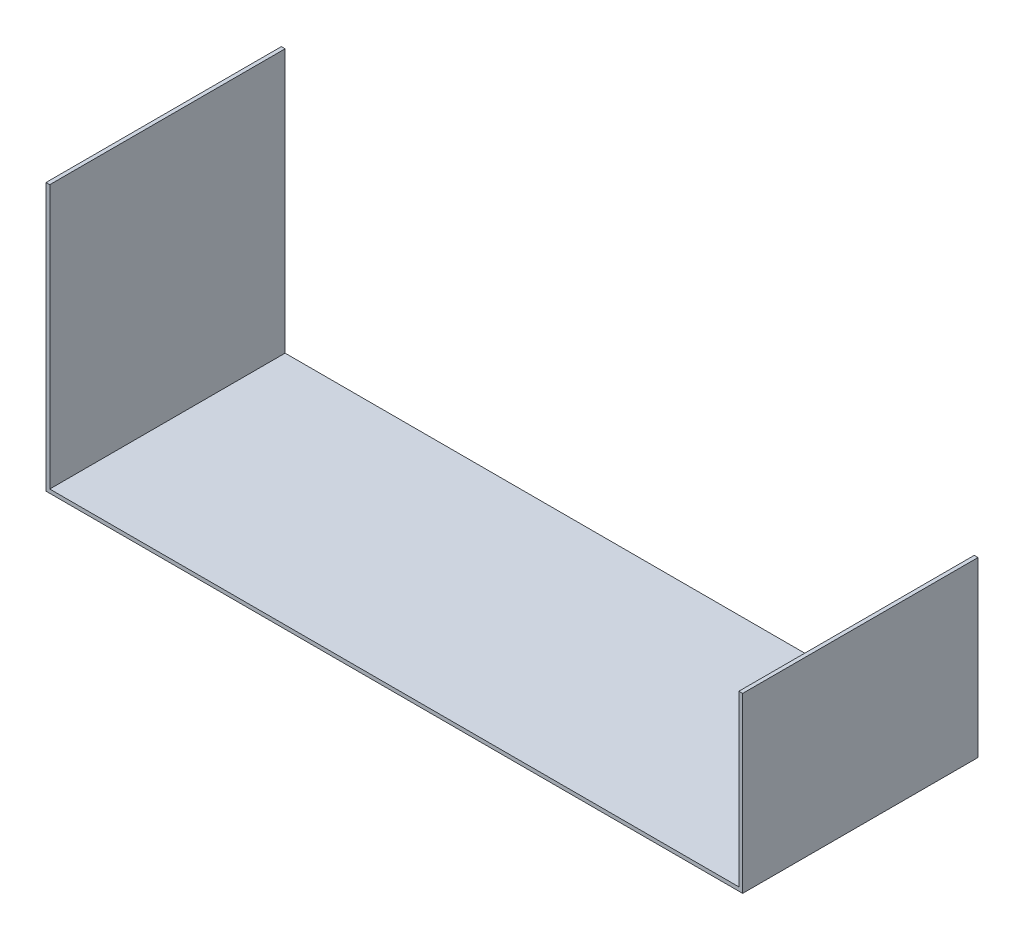
SolidWorks part; units mm, degrees
ref_plane "前视基准面" through (0, 0, 0) normal (0, 0, 1) x (1, 0, 0)
ref_plane "上视基准面" through (0, 0, 0) normal (0, 1, 0) x (1, 0, 0)
ref_plane "右视基准面" through (0, 0, 0) normal (1, 0, 0) x (0, 0, -1)
sketch "草图1" plane through (0, 0, 0) normal (0, 0, 1) x (1, 0, 0)
  line L0 (0, 0) -> (370, 0)
  line L1 (370, 0) -> (370, 92)
  line L2 (0, 0) -> (0, 142)
  line L3 (368, 2) -> (368, 92)
  line L4 (2, 2) -> (368, 2)
  line L5 (2, 2) -> (2, 142)
  line L6 (0, 142) -> (2, 142)
  line L7 (368, 92) -> (370, 92)
  dimension "D1" = 370
  dimension "D2" = 142
  dimension "D3" = 92
  dimension "D4" = 2
extrude "凸台-拉伸1" add sketch "草图1" along normal blind 125
